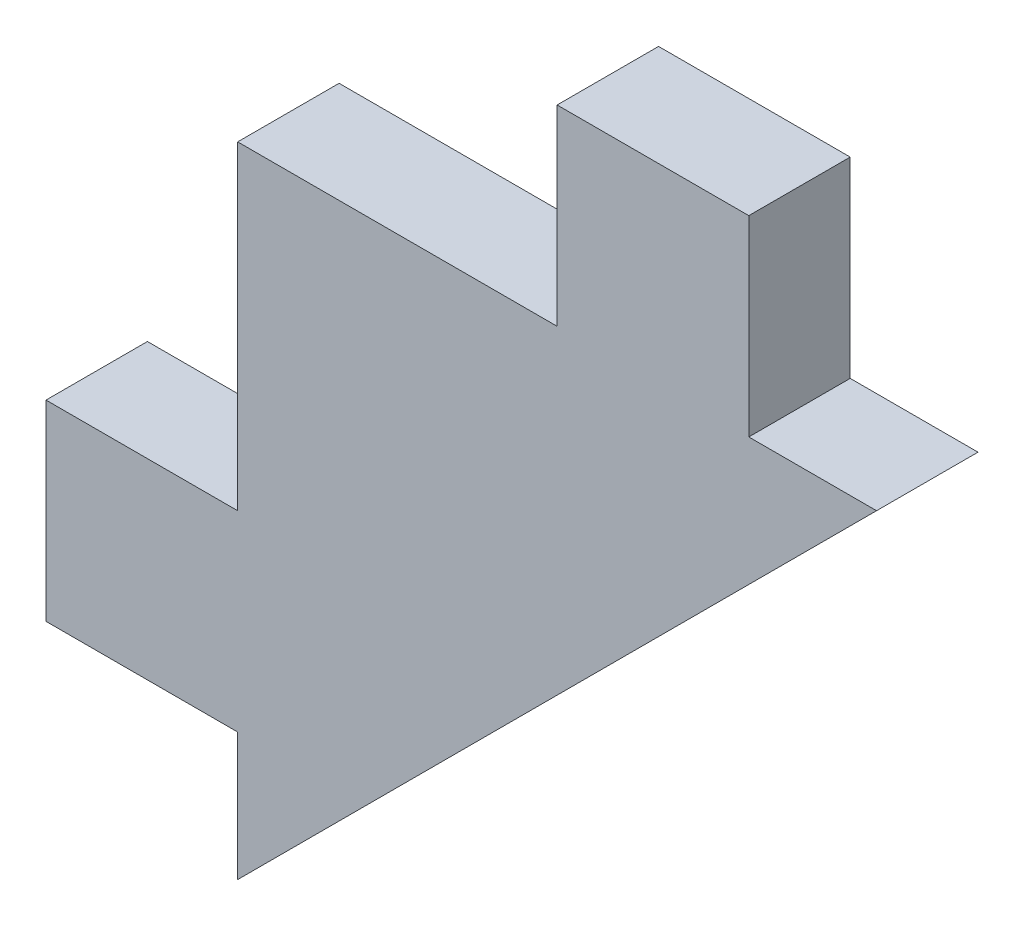
SolidWorks part; units mm, degrees
ref_plane "Front Plane" through (0, 0, 0) normal (0, 0, 1) x (1, 0, 0)
ref_plane "Top Plane" through (0, 0, 0) normal (0, 1, 0) x (1, 0, 0)
ref_plane "Right Plane" through (0, 0, 0) normal (1, 0, 0) x (0, 0, -1)
sketch "Sketch2" plane through (0, 0, 0) normal (0, 0, 1) x (1, 0, 0)
  line L0 (0, 20) -> (0, 10)
  line L1 (0, -55) -> (0, 55) construction
  line L2 (0, 20) -> (10, 20)
  line L3 (20, 20) -> (0, 0)
  line L4 (10, 20) -> (10, 26)
  line L5 (10, 26) -> (16, 26)
  line L6 (16, 26) -> (16, 20)
  line L7 (0, 10) -> (-6, 10)
  line L8 (-6, 10) -> (-6, 4)
  line L9 (-6, 4) -> (0, 4)
  line L10 (0, 4) -> (0, 0)
  line L11 (16, 20) -> (20, 20)
  dimension "D1" = 20
  dimension "D2" = 6
  dimension "D3" = 6
  dimension "D4" = 16
extrude "Boss-Extrude1" add sketch "Sketch2" along normal blind 3.175
